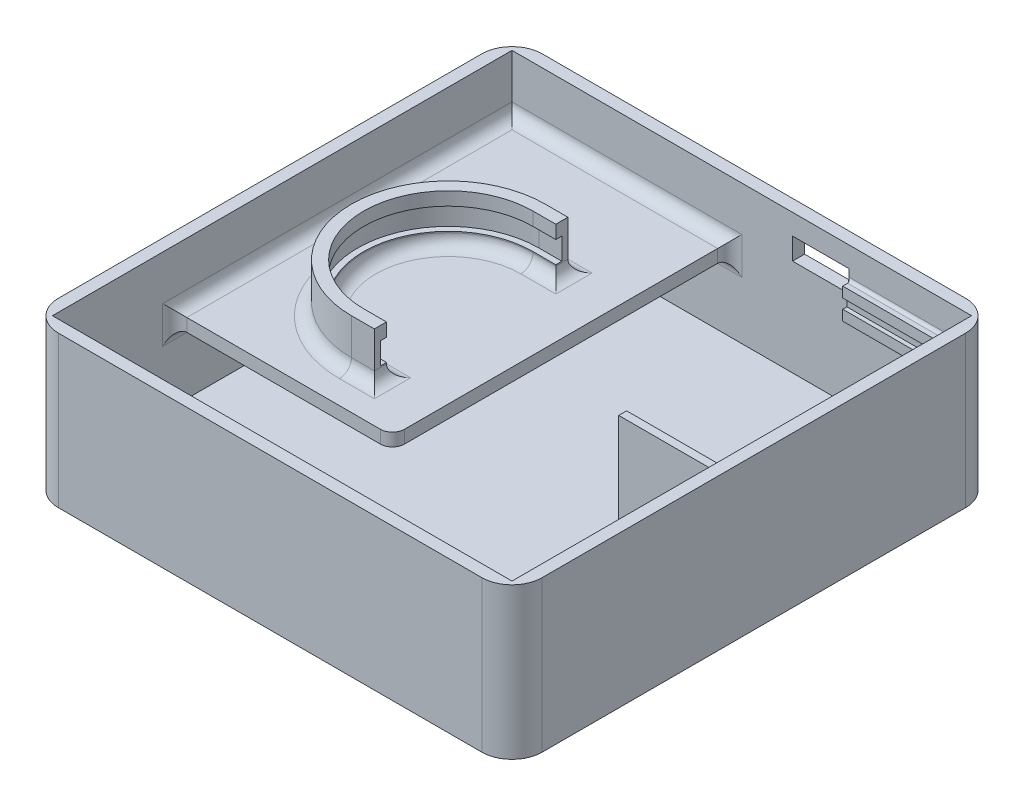
SolidWorks part; units mm, degrees
ref_plane "Front Plane" through (0, 0, 0) normal (0, 0, 1) x (1, 0, 0)
ref_plane "Top Plane" through (0, 0, 0) normal (0, 1, 0) x (1, 0, 0)
ref_plane "Right Plane" through (0, 0, 0) normal (1, 0, 0) x (0, 0, -1)
sketch "Sketch1" plane through (0, 0, 0) normal (0, 1, 0) x (1, 0, 0)
  line L1 (0, 0) -> (80, 0)
  line L2 (0, 0) -> (0, -80)
  line L3 (0, -80) -> (80, -80)
  line L4 (80, 0) -> (80, -80)
  dimension "D1" = 80
  dimension "D2" = 80
extrude "Boss-Extrude1" add sketch "Sketch1" along normal blind 25
shell "Shell1" thickness 2 removed face at (40, 25, 40)
sketch "Sketch2" plane through (78, 0, 0) normal (-1, 0, 0) x (0, 0, 1)
  line L1 (39.0414, 18.1849) -> (39.7266, 18.1849)
  line L6 (39.7266, 18.1849) -> (39.7266, 16.5849)
  line L15 (2, 19.8979) -> (2, 14.8719)
  line L31 (2, 25) -> (2, 2) construction
  line L32 (2, 14.8719) -> (3.3118, 14.8719)
  line L33 (3.3118, 14.8719) -> (3.3118, 16.5849)
  line L34 (3.3118, 16.5849) -> (2.6266, 16.5849)
  line L35 (2.6266, 16.5849) -> (2.6266, 18.1849)
  line L36 (2.6266, 18.1849) -> (3.3118, 18.1849)
  line L37 (3.3118, 18.1849) -> (3.3118, 19.8979)
  line L38 (3.3118, 19.8979) -> (2, 19.8979)
  line L39 (39.7266, 16.5849) -> (39.0414, 16.5849)
  line L40 (39.0414, 16.5849) -> (39.0414, 2)
  line L41 (78, 2) -> (2, 2) construction
  line L42 (39.0414, 2) -> (40.3532, 2)
  line L43 (39.0414, 18.1849) -> (39.0414, 19.8979)
  line L45 (39.0414, 19.8979) -> (40.3532, 19.8979)
  line L46 (40.3532, 19.8979) -> (40.3532, 2)
  point P12 (-22.441, 16.076)
  point P21 (10.661, 12.5537)
  dimension "D1" = 1.6
  dimension "D3" = 37.1
extrude "Boss-Extrude2" add sketch "Sketch2" along normal blind 20
sketch "Sketch3" plane through (0, 0, 2) normal (0, 0, 1) x (1, 0, 0)
  line L1 (48.3822, 21.5999) -> (57.7478, 21.5999)
  line L2 (48.3822, 21.5999) -> (48.3822, 18.0124)
  line L3 (48.3822, 18.0124) -> (57.7478, 18.0124)
  line L4 (57.7478, 21.5999) -> (57.7478, 18.0124)
extrude "Cut-Extrude1" cut sketch "Sketch3" against normal up to surface (2 mm away) up to face at (40, 12.5, 0)
sketch "Sketch5" plane through (0, 2, 0) normal (0, 1, 0) x (1, 0, 0)
  line L10 (61.325, -5.3766) -> (61.1595, -5.211) construction
  line L11 (61.1595, -5.211) -> (64.4905, -5.211)
  line L12 (61.1595, -5.211) -> (61.1595, -8.5421)
  line L13 (61.1595, -8.5421) -> (64.4905, -8.5421)
  line L14 (64.4905, -5.211) -> (64.4905, -8.5421)
  line L15 (61.325, -8.3766) -> (61.1595, -8.5421) construction
  line L16 (61.325, -8.3766) -> (64.325, -8.3766) construction
  line L17 (61.325, -5.3766) -> (61.325, -8.3766) construction
  line L18 (64.4905, -8.5421) -> (64.325, -8.3766) construction
  line L19 (64.325, -5.3766) -> (64.4905, -5.211) construction
  dimension "D2" = 45
extrude "Cut-Extrude3" cut sketch "Sketch5" against normal up to surface (2 mm away) up to face at (40, 0, 40)
sketch "Sketch6" plane through (0, 2, 0) normal (0, 1, 0) x (1, 0, 0)
  circle A0 centre (8.0346, -17.3538) radius 1.5
  circle A1 centre (8.0346, -62.6462) radius 1.5
  circle A2 centre (71.9654, -62.6462) radius 1.5
  circle A3 centre (71.9654, -17.3538) radius 1.5
extrude "Cut-Extrude4" cut sketch "Sketch6" against normal up to surface (2 mm away) up to face at (62.825, 0, 6.8766)
sketch "Sketch9" plane through (2, 0, 0) normal (1, 0, 0) x (0, 0, -1)
  line L0 (-2, 25) -> (-2, 2) construction
  line L1 (-2, 13.5) -> (-57.77, 13.5)
  line L2 (-2, 13.5) -> (-2, 15.6276)
  line L3 (-2, 15.6276) -> (-57.77, 15.6276)
  line L4 (-57.77, 13.5) -> (-57.77, 15.6276)
extrude "Boss-Extrude4" add sketch "Sketch9" along normal blind 36
sketch "Sketch7" plane through (0, 15.6276, 0) normal (0, 1, 0) x (1, 0, 0)
  line L9 (29.1404, -51.9019) -> (29.1404, -49.8999)
  line L10 (29.1404, -51.9019) -> (25.366, -51.9019)
  line L11 (25.366, -49.8999) -> (29.1404, -49.8999)
  line L12 (29.1404, -21.9039) -> (29.1404, -19.9019)
  line L13 (25.366, -19.9019) -> (29.1404, -19.9019)
  line L14 (25.366, -21.9039) -> (29.1404, -21.9039)
  arc A2 (25.366, -19.9019) -> (25.366, -51.9019) centre (25.366, -35.9019) ccw
  arc A3 (25.366, -21.9039) -> (25.366, -49.8999) centre (25.366, -35.9019) ccw
  point P0 (0, 0)
extrude "Boss-Extrude3" add sketch "Sketch7" along normal blind 8
ref_plane "Plane1" through (0, 19.6276, 0) normal (0, 1, 0) x (1, 0, 0)
sketch "Sketch8" plane through (0, 19.6276, 0) normal (0, 1, 0) x (1, 0, 0)
  line L13 (29.1404, -50.8999) -> (25.366, -50.8999)
  line L22 (25.366, -20.9039) -> (29.1404, -20.9039)
  line L23 (29.1404, -49.8999) -> (25.366, -49.8999)
  line L24 (25.366, -21.9039) -> (29.1404, -21.9039)
  line L25 (29.1404, -49.8999) -> (25.366, -49.8999)
  line L26 (25.366, -21.9039) -> (29.1404, -21.9039)
  line L27 (29.1404, -20.9039) -> (29.1404, -21.9039)
  line L28 (29.1404, -50.8999) -> (29.1404, -49.8999)
  arc A6 (25.366, -20.9039) -> (25.366, -50.8999) centre (25.366, -35.9019) ccw
  arc A7 (25.366, -21.9039) -> (25.366, -49.8999) centre (25.366, -35.9019) ccw
  arc A8 (25.366, -21.9039) -> (25.366, -49.8999) centre (25.366, -35.9019) ccw
  dimension "D1" = 0
  dimension "D2" = 1
extrude "Cut-Extrude5" cut sketch "Sketch8" against normal blind 1.8 and the other way blind 1.8
fillet "Fillet1" radius 2 15 edges at (27.2532, 15.6276, 49.8999) (27.2532, 15.6276, 21.9039) (27.2532, 15.6276, 19.9019) (27.2532, 15.6276, 51.9019) (38, 14.5638, 2) (2, 15.6276, 29.885) (20, 15.6276, 2) (11.3681, 15.6276, 35.9019) (29.1404, 15.6276, 20.9029) (29.1404, 15.6276, 50.9009) (9.366, 15.6276, 35.9019) (2, 14.5638, 57.77) (2, 13.5, 29.885) (20, 13.5, 2) (38, 14.5638, 57.77)
fillet "Fillet2" radius 0.5 14 edges at (78, 14.8719, 2.6559) (58, 2, 39.6973) (78, 19.0414, 3.3118) (78, 15.7284, 3.3118) (68, 19.8979, 2) (58, 17.3849, 2) (68, 14.8719, 2) (78, 19.0414, 39.0414) (78, 19.8979, 39.6973) (78, 10.949, 40.3532) (68, 2, 40.3532) (78, 9.2925, 39.0414) (68, 2, 39.0414) (78, 19.8979, 2.6559)
fillet "Fillet3" radius 0.5 4 edges at (61.1595, 1, 5.211) (64.4905, 1, 5.211) (64.4905, 1, 8.5421) (61.1595, 1, 8.5421)
fillet "Fillet4" radius 5 4 edges at (0, 12.5, 0) (80, 12.5, 0) (80, 12.5, 80) (0, 12.5, 80)
